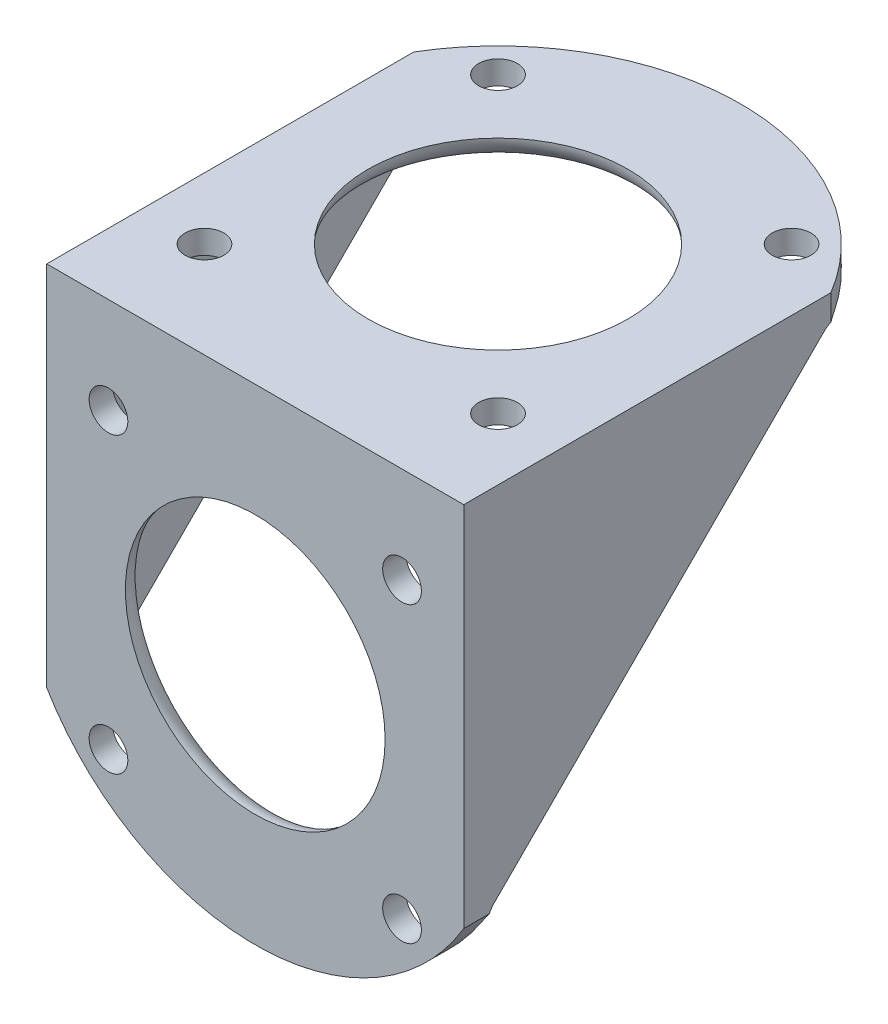
SolidWorks part; units mm, degrees
material "6061-T6 (SS)"
ref_plane "Front Plane" through (0, 0, 0) normal (0, 0, 1) x (1, 0, 0)
ref_plane "Top Plane" through (0, 0, 0) normal (0, 1, 0) x (1, 0, 0)
ref_plane "Right Plane" through (0, 0, 0) normal (1, 0, 0) x (0, 0, -1)
sketch "Sketch1" plane through (0, 0, 0) normal (0, 0, 1) x (1, 0, 0)
  line L0 (-12.5158, 12.5158) -> (-12.5158, -12.5158) construction
  line L1 (-12.5158, -12.5158) -> (12.5158, -12.5158) construction
  line L2 (12.5158, -12.5158) -> (12.5158, 12.5158) construction
  line L3 (12.5158, 12.5158) -> (-12.5158, 12.5158) construction
  line L4 (0, 0) -> (29.0927, 0) construction
  line L5 (0, 0) -> (-27.6955, 0) construction
  line L6 (-27.6955, 10.9507) -> (-27.6955, -10.9507) construction
  line L7 (29.0927, 10.9507) -> (29.0927, -10.9507) construction
  line L10 (-17.78, -10.602) -> (-17.78, 20.701)
  line L11 (-17.78, 20.701) -> (17.78, 20.701)
  line L12 (17.78, -10.602) -> (17.78, 20.701)
  circle A0 centre (0, 0) radius 17.7 construction
  arc A1 (-17.78, -10.602) -> (17.78, -10.602) centre (0, 0) ccw
  circle A2 centre (-12.5158, -12.5158) radius 1.651
  circle A3 centre (12.5158, -12.5158) radius 1.651
  circle A4 centre (12.5158, 12.5158) radius 1.651
  circle A5 centre (-12.5158, 12.5158) radius 1.651
  circle A6 centre (0, 0) radius 11.0731
  dimension "D1" = 41.402
  dimension "D5" = 3.302
  dimension "D6" = 3.302
  dimension "D7" = 3.302
  dimension "D8" = 3.302
  dimension "D9" = 22.1463
  dimension "D2" = 35.56
  dimension "D3" = 17.78
  dimension "D4" = 20.701
extrude "Boss-Extrude1" add sketch "Sketch1" along normal blind 2
ref_plane "Plane1" through (0, 9.3505, -9.3505) normal (0, -0.7071, 0.7071) x (1, 0, 0)
mirror "Mirror1" about plane through (0, 9.3505, -9.3505) normal (0, -0.7071, 0.7071) of "Boss-Extrude1"
sketch "Sketch2" plane through (-17.78, 0, 0) normal (-1, 0, 0) x (0, 0, 1)
  line L0 (0, -10.602) -> (-29.303, 18.701)
  line L1 (-29.303, 18.701) -> (0, 18.701)
  line L2 (0, 18.701) -> (0, -10.602) construction
  line L3 (0, 18.701) -> (-29.303, 18.701) construction
  line L4 (0, 18.701) -> (0, -10.602)
extrude "Boss-Extrude2" add sketch "Sketch2" against normal blind 2
mirror "Mirror2" about plane through (0, 0, 0) normal (1, 0, 0) of "Boss-Extrude2"
fillet "Fillet2" radius 2 2 edges at (11.0731, 18.701, -18.701) (11.0731, 0, 0)
fillet "Fillet3" radius 2 4 edges at (16.78, -10.602, 0) (-16.78, -10.602, 0) (-16.78, 18.701, -29.303) (16.78, 18.701, -29.303)
equation "\"D3@Sketch1\"=\"D2@Sketch1\"/2"
equation "\"D4@Sketch1\"=\"D1@Sketch1\"/2"
equation "\"D6@Sketch1\"=\"D5@Sketch1\""
equation "\"D7@Sketch1\"=\"D6@Sketch1\""
equation "\"D8@Sketch1\"=\"D7@Sketch1\""
